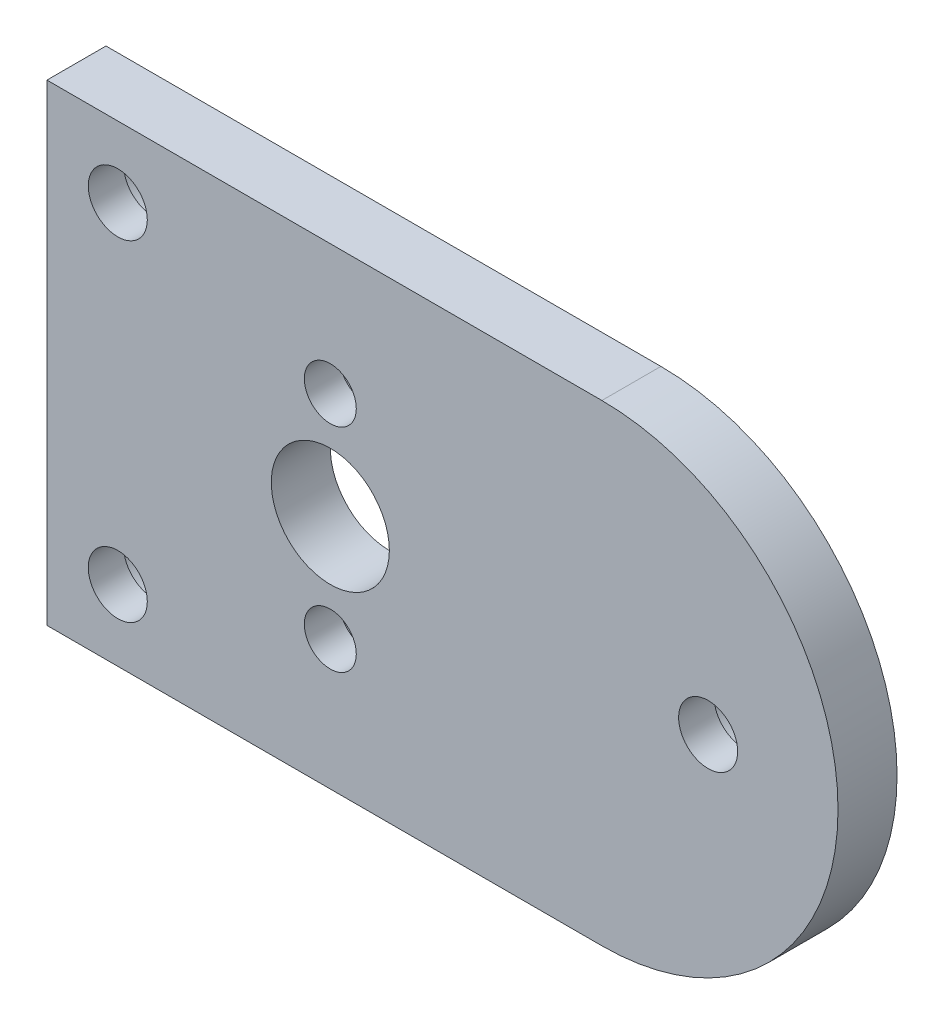
SolidWorks part; units mm, degrees
ref_plane "前视基准面" through (0, 0, 0) normal (0, 0, 1) x (1, 0, 0)
ref_plane "上视基准面" through (0, 0, 0) normal (0, 1, 0) x (1, 0, 0)
ref_plane "右视基准面" through (0, 0, 0) normal (1, 0, 0) x (0, 0, -1)
other "Configuration Table"
sketch "草图1" plane through (0, 0, 0) normal (0, 0, 1) x (1, 0, 0)
  line L0 (0, 4.5) -> (0, -4.5) construction
  line L1 (-11.5, -10) -> (11.5, -10)
  line L2 (-11.5, -10) -> (-11.5, 10)
  line L3 (-11.5, 10) -> (11.5, 10)
  line L4 (11.5, -10) -> (11.5, 10)
  line L5 (-11.5, -10) -> (11.5, 10) construction
  line L6 (-11.5, 10) -> (11.5, -10) construction
  line L8 (-11.5, 10) -> (-12, 10)
  line L9 (-11.5, 10) -> (-11.5, -10)
  line L10 (-11.5, -10) -> (-12, -10)
  line L11 (-12, 10) -> (-12, -10)
  circle A4 centre (0, 4.5) radius 0.85
  circle A5 centre (0, -4.5) radius 0.85
  circle A6 centre (0, 4.5) radius 1.1
  circle A7 centre (0, -4.5) radius 1.1
  circle A8 centre (0, 0) radius 2.5
  circle A9 centre (-9, 7) radius 1.25
  circle A10 centre (-9, 7) radius 2
  circle A11 centre (-9, -7) radius 1.25
  circle A12 centre (-9, -7) radius 2
  circle A14 centre (11.5, 0) radius 10
  circle A15 centre (16, 0) radius 1.25
  circle A16 centre (16, 0) radius 2
  point P0 (0, 0)
  point P22 (0, 0)
  point P25 (-7.7363, 2.0372)
  point P26 (-8.9509, 7.2037)
  point P27 (7.1163, 0)
  point P28 (-8.439, -8.0982)
  point P32 (16.0099, 0)
  point P33 (0, 0)
  dimension "D1" = 1.7
  dimension "D2" = 1.7
  dimension "D3" = 2.2
  dimension "D5" = 5
  dimension "D8" = 2.5
  dimension "D9" = 4
  dimension "D4" = 9
  dimension "D6" = 11.5
  dimension "D7" = 20
  dimension "D10" = 3
  dimension "D11" = 3
  dimension "D12" = 0.5
  dimension "D13" = 3
  dimension "D14" = 16
extrude "凸台-拉伸1" add sketch "草图1" along normal mid plane 2.5 contours L8 L11 L10 L2 | L4 A14 | A16 A15 | L2 L3 L4 L1 | A4 | A5 | A8 | A9 | A11 region at (-11.75, 0, 0) region at (11.7236, 0, 0) region at (14.0566, 0, 0)
extrude "切除-拉伸1" cut sketch "草图1<4>" against normal offset from surface (1.5 mm away) 1 from surface contours A6 | A7 up to face at (2.25, 0, -1.25) starting at face at (2.25, 0, 1.25)
sketch "草图1<4>" plane through (0, 0, 0) normal (0, 0, 1) x (1, 0, 0) same geometry as "草图1"
extrude "切除-拉伸3" cut sketch "草图1<5>" along normal offset from surface (1 mm away) 1.5 from surface contours A16 | A12 | A10 up to face at (1.1, 4.5, 1.25) starting at face at (2.25, 0, -1.25)
sketch "草图1<5>" plane through (0, 0, 0) normal (0, 0, 1) x (1, 0, 0) same geometry as "草图1"
